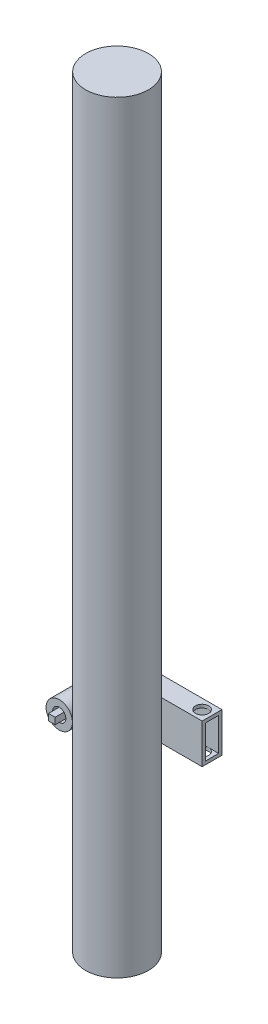
SolidWorks part; units mm, degrees
ref_plane "Front Plane" through (0, 0, 0) normal (0, 0, 1) x (1, 0, 0)
ref_plane "Top Plane" through (0, 0, 0) normal (0, 1, 0) x (1, 0, 0)
ref_plane "Right Plane" through (0, 0, 0) normal (1, 0, 0) x (0, 0, -1)
sketch "Elevation Bar" plane through (0, 0, 0) normal (0, 1, 0) x (1, 0, 0)
  circle A0 centre (0, 0) radius 30.226
  dimension "D1" = 60.452
extrude "Elevation Bar Part" add sketch "Elevation Bar" along normal blind 734.06
sketch "Pole and Drivetrain Pos" plane through (0, 0, 0) normal (0, 0, 1) x (1, 0, 0)
  line L0 (0, 0) -> (172.1794, 0) construction
  line L1 (-30.226, 0) -> (-30.226, 734.06) construction
  line L2 (-30.226, 734.06) -> (30.226, 734.06) construction
  line L3 (30.226, 734.06) -> (30.226, 0) construction
  line L4 (30.226, 0) -> (30.226, 734.06) construction
  line L5 (636.651, 41.275) -> (27.051, 41.275) construction
  line L6 (636.651, 53.975) -> (27.051, 53.975)
  line L7 (636.651, 53.975) -> (636.651, 28.575)
  line L8 (636.651, 28.575) -> (27.051, 28.575)
  line L9 (27.051, 53.975) -> (27.051, 28.575)
  line L10 (-30.226, 93.98) -> (30.226, 93.98) construction
  line L11 (33.2486, 0) -> (-33.2486, 0) construction
  line L12 (30.226, 185.42) -> (-30.226, 185.42) construction
  line L13 (30.226, 276.86) -> (-30.226, 276.86) construction
  line L14 (30.226, 368.3) -> (-30.226, 368.3) construction
  line L15 (30.226, 459.74) -> (-30.226, 459.74) construction
  line L16 (30.226, 551.18) -> (-30.226, 551.18) construction
  line L17 (30.226, 642.62) -> (-30.226, 642.62) construction
  line L18 (30.226, 73.152) -> (750.8896, 73.152) construction
  circle A0 centre (579.501, 41.275) radius 41.275 construction
  circle A1 centre (84.201, 41.275) radius 41.275 construction
  circle A2 centre (331.851, 41.275) radius 41.275 construction
  circle A3 centre (84.201, 41.275) radius 25.4
  point P24 (331.851, 41.275)
  point P28 (0, 0)
  point P45 (0, 0)
  dimension "D2" = 82.55
  dimension "D5" = 50.8
  dimension "D1" = 609.6
  dimension "D3" = 25.4
  dimension "D6" = 93.98
  dimension "D7" = 185.42
  dimension "D8" = 276.86
  dimension "D9" = 368.3
  dimension "D10" = 459.74
  dimension "D11" = 551.18
  dimension "D12" = 642.62
  dimension "D13" = 73.152
  dimension "D14" = 57.15
  dimension "D4" = 57.15
  dimension "D15" = 6.35
sketch "Driving Wheels Geo" plane through (0, 0, 0) normal (0, 0, 1) x (1, 0, 0)
  line L0 (-30.226, 182.88) -> (-30.226, 101.727) construction
  line L1 (55.626, 101.727) -> (30.226, 101.727) construction
  line L2 (-30.226, 0) -> (-30.226, 734.06) construction
  line L3 (30.226, 734.06) -> (30.226, 0) construction
  line L5 (30.226, 101.727) -> (-30.226, 101.727) construction
  line L6 (-30.226, 182.88) -> (30.226, 101.727) construction
  line L7 (31.8135, 101.727) -> (-30.226, 182.88) construction
  line L8 (30.226, 227.417) -> (203.668, 53.975) construction
  line L9 (-42.926, 195.58) -> (44.8729, 195.58) construction
  line L10 (30.226, 73.152) -> (750.8896, 73.152) construction
  line L11 (636.651, 53.975) -> (27.051, 53.975) construction
  line L14 (-42.926, 170.18) -> (44.8729, 170.18) construction
  line L15 (44.8729, 170.18) -> (44.8729, 195.58) construction
  line L16 (81.026, 28.575) -> (81.026, 257.175) construction
  line L17 (32.1729, 195.58) -> (57.5729, 195.58) construction
  line L18 (32.1729, 195.58) -> (32.1729, 170.18) construction
  line L19 (32.1729, 170.18) -> (57.5729, 170.18) construction
  line L20 (57.5729, 195.58) -> (57.5729, 170.18) construction
  line L21 (32.1729, 195.58) -> (57.5729, 170.18) construction
  line L22 (32.1729, 170.18) -> (57.5729, 195.58) construction
  line L23 (636.651, 28.575) -> (27.051, 28.575) construction
  line L24 (284.226, 257.175) -> (81.026, 257.175) construction
  line L25 (284.226, 257.175) -> (284.226, 53.975) construction
  line L26 (81.026, 257.175) -> (30.226, 257.175) construction
  circle A1 centre (55.626, 101.727) radius 25.4
  circle A3 centre (-42.926, 182.88) radius 12.7
  circle A4 centre (81.026, 104.775) radius 50.8 construction
  circle A5 centre (55.626, 101.727) radius 23.8125 construction
  circle A7 centre (284.226, 257.175) radius 203.2 construction
  point P28 (44.8729, 182.88)
  dimension "D1" = 50.8
  dimension "D2" = 1.5875
  dimension "D3" = 52.603
  dimension "D4" = 3.175
  dimension "D5" = 182.88
  dimension "D8" = 101.6
  dimension "D6" = 25.4
  dimension "D13" = 3.175
  dimension "D14" = 50.8
  dimension "D16" = 406.4
  dimension "D7" = 81.153
  dimension "D9" = 45
  dimension "D10" = 53.317
  dimension "D11" = 25.4
  dimension "D12" = 47.752
ref_plane "Plane1" through (0, 182.88, 0) normal (0, 1, 0) x (1, 0, 0)
sketch "Clamp Geo" plane through (0, 182.88, 0) normal (0, 1, 0) x (1, 0, 0)
  line L0 (-42.926, -19.8438) -> (-42.926, 50.8635) construction
  line L3 (27.051, 228.6) -> (27.051, -228.6) construction
  line L4 (50.0464, 31.8135) -> (-49.276, 31.8135)
  line L5 (50.0464, 31.8135) -> (50.0464, 50.8635)
  line L6 (50.0464, 50.8635) -> (-49.276, 50.8635)
  line L7 (-49.276, 31.8135) -> (-49.276, 50.8635)
  line L10 (-46.101, 50.8635) -> (-39.751, 50.8635)
  line L11 (-46.101, 50.8635) -> (-46.101, -19.8438)
  line L12 (-46.101, -19.8438) -> (-39.751, -19.8438)
  line L13 (-39.751, 50.8635) -> (-39.751, -19.8438)
  line L14 (-55.626, 12.7) -> (-30.226, 12.7) construction
  line L15 (-55.626, 12.7) -> (-55.626, -12.7) construction
  line L16 (-55.626, -12.7) -> (-30.226, -12.7) construction
  line L17 (-30.226, 12.7) -> (-30.226, -12.7) construction
  line L18 (-55.626, 12.7) -> (-30.226, -12.7) construction
  line L19 (-55.626, -12.7) -> (-30.226, 12.7) construction
  line L20 (0, -30.226) -> (0, 30.226) construction
  line L21 (-30.226, 0) -> (30.226, 0) construction
  line L22 (-46.101, 46.101) -> (-42.926, 46.101) construction
  line L23 (-39.751, 41.3385) -> (-46.101, 41.3385)
  line L24 (-46.101, 41.3385) -> (-46.101, 50.8635) construction
  line L25 (-39.751, 31.8135) -> (-39.751, 50.8635) construction
  line L26 (50.0464, 41.3385) -> (40.5214, 41.3385) construction
  circle A0 centre (0, 0) radius 30.226 construction
  circle A3 centre (-42.926, 46.101) radius 1.8288
  circle A5 centre (-42.926, 36.576) radius 1.8288
  circle A6 centre (40.5214, 41.3385) radius 6.35
  circle A7 centre (40.5214, 41.3385) radius 13.4704 construction
  point P14 (-42.926, 0)
  point P32 (-39.751, 41.3385)
  point P34 (-46.101, 41.3385)
  point P36 (-42.926, 41.3385)
  point P42 (50.0464, 41.3385)
  dimension "D1" = 60.452
  dimension "D4" = 1.5875
  dimension "D7" = 3.6576
  dimension "D8" = 3.175
  dimension "D10" = 12.7
  dimension "D11" = 3.175
  dimension "D2" = 457.2
  dimension "D3" = 19.05
  dimension "D5" = 6.35
  dimension "D6" = 25.4
  dimension "D9" = 99.3224
  dimension "D13" = 7.1437
sketch "Locked Setting Geo" plane through (0, 182.88, 0) normal (0, 1, 0) x (1, 0, 0)
  line L0 (30.2525, 144.301) -> (91.1428, 108.3583) construction
  line L1 (27.477, 37.9778) -> (77.9656, 123.5104)
  line L2 (27.477, 37.9778) -> (43.8821, 28.2941)
  line L3 (43.8821, 28.2941) -> (94.3707, 113.8267)
  line L4 (77.9656, 123.5104) -> (94.3707, 113.8267)
  line L5 (92.7568, 111.0925) -> (89.5289, 105.6242)
  line L6 (92.7568, 111.0925) -> (31.8664, 147.0352)
  line L7 (31.8664, 147.0352) -> (28.6385, 141.5668)
  line L8 (89.5289, 105.6242) -> (28.6385, 141.5668)
  line L9 (64.7337, 138.6948) -> (51.8221, 116.8213) construction
  line L10 (64.7337, 138.6948) -> (42.8602, 151.6064) construction
  line L11 (42.8602, 151.6064) -> (29.9486, 129.7329) construction
  line L12 (51.8221, 116.8213) -> (29.9486, 129.7329) construction
  line L13 (64.7337, 138.6948) -> (29.9486, 129.7329) construction
  line L14 (42.8602, 151.6064) -> (51.8221, 116.8213) construction
  line L17 (88.6555, 113.5135) -> (87.0416, 110.7793) construction
  line L18 (81.3263, 110.466) -> (84.5542, 115.9344)
  line L19 (84.5542, 115.9344) -> (92.7568, 111.0925) construction
  line L20 (73.1238, 115.3079) -> (89.5289, 105.6242) construction
  line L21 (35.6795, 33.1359) -> (40.5214, 41.3385) construction
  line L22 (50.0464, 50.8635) -> (-49.276, 50.8635) construction
  line L23 (-46.101, 50.8635) -> (-46.101, -19.8438) construction
  line L24 (27.051, 228.6) -> (27.051, -228.6) construction
  circle A1 centre (87.0416, 110.7793) radius 1.8288
  circle A2 centre (78.839, 115.6211) radius 1.8288
  circle A3 centre (40.5214, 41.3385) radius 6.35
  point P10 (47.3411, 134.2138)
  point P28 (81.3263, 110.466)
  point P30 (84.5542, 115.9344)
  point P32 (82.9403, 113.2002)
  point P36 (35.6795, 33.1359)
  point P40 (40.5214, 41.3385)
  point P44 (-17.1792, 28.8062)
  dimension "D6" = 3.6576
  dimension "D9" = 12.7
  dimension "D2" = 19.05
  dimension "D3" = 1.5875
  dimension "D4" = 6.35
  dimension "D5" = 25.4
  dimension "D7" = 3.175
  dimension "D8" = 99.3224
  dimension "D10" = 3.175
  dimension "D11" = 50.8635
  dimension "D12" = 67.3197
extrude "Boss-Extrude1" add sketch "Clamp Geo" along normal blind 19.05 and the other way blind 19.05 separate body contours L6 L13 L4 L5 A6 | L11 L6 L7 L4 | L13 L23 L11 L4 A5 | L23 L13 L6 L11 A3 region at (2.3187, 182.88, -41.3385) region at (-42.926, 182.88, -31.928) region at (-47.6885, 182.88, -41.3385) region at (-42.926, 182.88, -41.453)
sketch "Sketch2" plane through (-49.276, 0, 0) normal (-1, 0, 0) x (0, 0, 1)
  line L0 (-41.3385, 201.93) -> (-41.3385, 163.83) construction
  line L1 (-31.8135, 201.93) -> (-50.8635, 201.93) construction
  line L2 (-31.8135, 163.83) -> (-50.8635, 163.83) construction
  line L3 (-31.8135, 163.83) -> (-31.8135, 201.93) construction
  line L4 (-47.6885, 167.005) -> (-34.9885, 167.005)
  line L5 (-47.6885, 167.005) -> (-47.6885, 198.755)
  line L6 (-47.6885, 198.755) -> (-34.9885, 198.755)
  line L7 (-34.9885, 167.005) -> (-34.9885, 198.755)
  line L8 (-47.6885, 167.005) -> (-34.9885, 198.755) construction
  line L9 (-47.6885, 198.755) -> (-34.9885, 167.005) construction
  point P6 (-41.3385, 182.88)
  dimension "D1" = 3.175
  dimension "D2" = 3.175
extrude "Cut-Extrude2" cut sketch "Sketch2" against normal up to surface (99.3224 mm away) up to face at (50.0464, 182.88, -41.3385)
sketch "Sketch3" plane through (0, 0, -50.8635) normal (0, 0, -1) x (-1, 0, 0)
  line L2 (39.7129, 179.6669) -> (46.1391, 179.6669)
  line L3 (39.7129, 179.6669) -> (39.7129, 186.0931)
  line L4 (39.7129, 186.0931) -> (46.1391, 186.0931)
  line L5 (46.1391, 179.6669) -> (46.1391, 186.0931)
  line L6 (39.7129, 179.6669) -> (46.1391, 186.0931) construction
  line L7 (39.7129, 186.0931) -> (46.1391, 179.6669) construction
  point P0 (42.926, 182.88)
  point P1 (42.926, 182.88)
  dimension "D1" = 6.4262
extrude "Cut-Extrude3" cut sketch "Sketch3" against normal up to surface (19.05 mm away) up to face at (0.3852, 182.88, -31.8135)
extrude "Boss-Extrude2" add sketch "Clamp Geo<3>" along normal blind 3.175 and the other way blind 3.175 separate body contours L13 L4 L11 L12 | L13 L23 L11 L4 A5 | L23 L13 L6 L11 A3 region at (-42.926, 182.88, -5.9849) region at (-42.926, 182.88, -31.928) region at (-42.926, 182.88, -41.453)
sketch "Clamp Geo<3>" plane through (0, 182.88, 0) normal (0, 1, 0) x (1, 0, 0) same geometry as "Clamp Geo"
sketch "Custom Driven Flywheel" plane through (0, 0, 0) normal (0, 0, 1) x (1, 0, 0)
  circle A0 centre (-42.926, 182.88) radius 12.7 construction
  circle A1 centre (-42.926, 182.88) radius 12.7
  circle A2 centre (-42.926, 182.88) radius 6.35
  dimension "D1" = 12.7
extrude "Boss-Extrude3" add sketch "Custom Driven Flywheel" along normal mid plane 25.4 separate body
sketch "Sketch8" plane through (0, 167.005, 0) normal (0, 1, 0) x (1, 0, 0)
  line L0 (-42.926, 47.6885) -> (-42.926, 34.9885) construction
  line L1 (-49.276, 34.9885) -> (-36.576, 34.9885) construction
  line L2 (-49.276, 34.9885) -> (-49.276, 47.6885)
  line L3 (-49.276, 47.6885) -> (-36.576, 47.6885) construction
  line L4 (-36.576, 34.9885) -> (-36.576, 47.6885)
  line L5 (-36.576, 41.3385) -> (-42.926, 41.3385) construction
  line L6 (-42.926, 41.3385) -> (-49.276, 41.3385) construction
  line L7 (-43.8339, 34.9885) -> (-49.276, 34.9885)
  line L8 (-43.8339, 47.6885) -> (-49.276, 47.6885)
  line L9 (-42.0181, 34.9885) -> (-36.576, 34.9885)
  line L10 (-42.0181, 47.6885) -> (-36.576, 47.6885)
  arc A0 (-43.8339, 47.6885) -> (-42.0181, 47.6885) centre (-42.926, 46.101) ccw construction
  arc A2 (-42.0181, 34.9885) -> (-43.8339, 34.9885) centre (-42.926, 36.576) ccw construction
  arc A3 (-43.8339, 47.6885) -> (-42.0181, 47.6885) centre (-42.926, 46.101) ccw
  arc A4 (-42.0181, 34.9885) -> (-43.8339, 34.9885) centre (-42.926, 36.576) ccw
extrude "Boss-Extrude5" add sketch "Sketch8" along normal up to surface (15.875 mm away) separate body up to plane "Plane1"
sketch "Sketch10" plane through (0, 182.88, 0) normal (0, 1, 0) x (1, 0, 0)
  line L0 (-36.576, 41.3385) -> (-49.276, 41.3385) construction
  line L1 (-36.576, 34.9885) -> (-36.576, 47.6885) construction
  line L2 (-49.276, 47.6885) -> (-49.276, 34.9885) construction
  line L3 (-49.276, 34.9885) -> (-43.8339, 34.9885) construction
  line L4 (-46.1391, 34.9885) -> (-39.7129, 34.9885)
  line L5 (-46.1391, 34.9885) -> (-46.1391, 47.6885)
  line L6 (-46.1391, 47.6885) -> (-39.7129, 47.6885)
  line L7 (-39.7129, 34.9885) -> (-39.7129, 47.6885)
  line L8 (-46.1391, 34.9885) -> (-39.7129, 47.6885) construction
  line L9 (-46.1391, 47.6885) -> (-39.7129, 34.9885) construction
  point P6 (-42.926, 41.3385)
  dimension "D1" = 6.4262
extrude "Cut-Extrude5" cut sketch "Sketch10" against normal blind 6.3881
ref_plane "Plane2" through (0, 0, 210.82) normal (0, 0, 1) x (1, 0, 0)
ref_plane "Plane3" through (0, 0, 166.37) normal (0, 0, 1) x (1, 0, 0)
sketch "Sketch12" plane through (0, 0, 166.37) normal (0, 0, 1) x (1, 0, 0)
  line L0 (636.651, 41.275) -> (27.051, 41.275) construction
  line L1 (636.651, 41.275) -> (27.051, 41.275) construction
  line L2 (84.201, 41.275) -> (96.901, 41.275) construction
  line L3 (109.601, 41.275) -> (109.601, 85.2691) construction
  circle A0 centre (84.201, 41.275) radius 25.4 construction
  circle A1 centre (84.201, 41.275) radius 25.4
  circle A2 centre (55.626, 101.727) radius 21.1667
  circle A4 centre (86.8604, 107.4259) radius 10.5833
  circle A5 centre (128.651, 41.275) radius 19.05
  circle A7 centre (86.8604, 107.4259) radius 21.1667
  circle A8 centre (109.601, 85.2691) radius 10.5833
  circle A9 centre (109.601, 85.2691) radius 25.4
  circle A10 centre (84.201, 41.275) radius 3.175 construction
  circle A11 centre (96.901, 41.275) radius 3.175 construction
  circle A12 centre (109.601, 41.275) radius 3.175 construction
  circle A13 centre (122.301, 41.275) radius 3.175 construction
  circle A14 centre (135.001, 41.275) radius 3.175 construction
  circle A15 centre (147.701, 41.275) radius 3.175 construction
  circle A16 centre (160.401, 41.275) radius 3.175 construction
  circle A17 centre (173.101, 41.275) radius 3.175 construction
  circle A18 centre (185.801, 41.275) radius 3.175 construction
  circle A19 centre (198.501, 41.275) radius 3.175 construction
  point P3 (55.626, 101.727)
  dimension "D1" = 42.3333
  dimension "D2" = 21.1667
  dimension "D3" = 50.8
  dimension "D4" = 38.1
  dimension "D5" = 42.3333
  dimension "D6" = 21.1667
  dimension "D8" = 6.35
  dimension "D10" = 12.7
  dimension "D9" = 10
sketch "Sketch13" plane through (0, 0, 210.82) normal (0, 0, 1) x (1, 0, 0)
  line L0 (109.601, 72.5691) -> (109.601, 97.9691) construction
  line L2 (90.551, 72.5691) -> (90.551, 97.9691)
  line L4 (154.051, 72.5691) -> (154.051, 97.9691)
  line L5 (147.701, 85.2691) -> (147.701, 41.275) construction
  line L6 (109.601, 85.2691) -> (154.051, 85.2691) construction
  line L7 (90.551, 85.2691) -> (109.601, 85.2691) construction
  line L8 (90.551, 97.9691) -> (109.601, 97.9691)
  line L9 (90.551, 72.5691) -> (109.601, 72.5691)
  line L10 (109.601, 97.9691) -> (154.051, 97.9691)
  line L11 (154.051, 72.5691) -> (109.601, 72.5691)
  circle A0 centre (109.601, 85.2691) radius 3.175 construction
  circle A1 centre (96.901, 85.2691) radius 3.175 construction
  circle A2 centre (147.701, 85.2691) radius 3.175 construction
  point P0 (109.601, 85.2691)
  dimension "D2" = 6.35
  dimension "D3" = 6.35
  dimension "D6" = 6.35
  dimension "D1" = 25.4
  dimension "D4" = 12.7
  dimension "D5" = 6.35
ref_plane "Plane5" through (0, 0, 146.177) normal (0, 0, 1) x (1, 0, 0)
sketch "Sketch15" plane through (0, 0, 146.177) normal (0, 0, 1) x (1, 0, 0)
  line L0 (90.551, 72.5691) -> (109.601, 72.5691) construction
  line L1 (154.051, 72.5691) -> (109.601, 72.5691) construction
  line L2 (154.051, 72.5691) -> (154.051, 97.9691) construction
  line L3 (109.601, 97.9691) -> (154.051, 97.9691) construction
  line L4 (90.551, 97.9691) -> (109.601, 97.9691) construction
  line L5 (90.551, 72.5691) -> (90.551, 97.9691) construction
  line L6 (90.551, 72.5691) -> (109.601, 72.5691)
  line L7 (154.051, 72.5691) -> (109.601, 72.5691)
  line L8 (154.051, 72.5691) -> (154.051, 97.9691)
  line L9 (109.601, 97.9691) -> (154.051, 97.9691)
  line L10 (90.551, 97.9691) -> (109.601, 97.9691)
  line L11 (90.551, 72.5691) -> (90.551, 97.9691)
  line L12 (90.551, 28.575) -> (109.601, 28.575)
  line L13 (154.051, 28.575) -> (109.601, 28.575)
  line L14 (154.051, 28.575) -> (154.051, 53.975)
  line L15 (109.601, 53.975) -> (154.051, 53.975)
  line L16 (90.551, 53.975) -> (109.601, 53.975)
  line L17 (90.551, 28.575) -> (90.551, 53.975)
  line L18 (154.051, 28.575) -> (90.551, 53.975) construction
  line L19 (109.601, 53.975) -> (109.601, 28.575) construction
  line L20 (154.051, 41.275) -> (90.551, 41.275) construction
  circle A0 centre (109.601, 85.2691) radius 3.175 construction
  circle A1 centre (109.601, 85.2691) radius 3.175
  circle A2 centre (109.601, 41.275) radius 3.175 construction
  point P19 (0, 0)
  point P20 (0, 0)
  point P21 (105.5783, 29.1431)
  point P23 (0, 0)
  dimension "D5" = 6.35
  dimension "D1" = 68.3916
  dimension "D2" = 68.3916
  dimension "D3" = 19.05
  dimension "D4" = 25.4
ref_plane "Plane6" through (0, 53.975, 0) normal (0, 1, 0) x (1, 0, 0)
sketch "Sketch16" plane through (0, 53.975, 0) normal (0, 1, 0) x (1, 0, 0)
  line L0 (27.051, -127) -> (27.051, 127)
  line L1 (33.401, 120.65) -> (33.401, 107.95) construction
  line L2 (27.051, 127) -> (39.751, 127)
  line L3 (27.051, 127) -> (27.051, -127)
  line L4 (27.051, -127) -> (39.751, -127)
  line L5 (39.751, 127) -> (39.751, -127)
  line L6 (33.401, 120.65) -> (33.401, 127) construction
  line L7 (135.001, -166.37) -> (135.001, -127) construction
  line L8 (636.651, 0) -> (27.051, 0) construction
  line L9 (128.651, 127) -> (141.351, 127)
  line L14 (128.651, 127) -> (128.651, -127)
  line L15 (128.651, -127) -> (141.351, -127)
  line L16 (141.351, 127) -> (141.351, -127)
  line L17 (128.651, 127) -> (141.351, -127) construction
  line L18 (128.651, -127) -> (141.351, 127) construction
  line L19 (135.001, -120.65) -> (135.001, -107.95) construction
  line L20 (135.001, -127) -> (135.001, -120.65) construction
  circle A0 centre (33.401, 120.65) radius 3.175
  circle A1 centre (33.401, 107.95) radius 3.175
  circle A2 centre (33.401, 95.25) radius 3.175
  circle A3 centre (33.401, 82.55) radius 3.175
  circle A4 centre (33.401, 69.85) radius 3.175
  circle A5 centre (33.401, 57.15) radius 3.175
  circle A6 centre (33.401, 44.45) radius 3.175
  circle A7 centre (33.401, 31.75) radius 3.175
  circle A8 centre (33.401, 19.05) radius 3.175
  circle A9 centre (33.401, 6.35) radius 3.175
  circle A10 centre (33.401, -6.35) radius 3.175
  circle A11 centre (33.401, -19.05) radius 3.175
  circle A12 centre (33.401, -31.75) radius 3.175
  circle A13 centre (33.401, -44.45) radius 3.175
  circle A14 centre (33.401, -57.15) radius 3.175
  circle A15 centre (33.401, -69.85) radius 3.175
  circle A16 centre (33.401, -82.55) radius 3.175
  circle A17 centre (33.401, -95.25) radius 3.175
  circle A18 centre (33.401, -107.95) radius 3.175
  circle A19 centre (33.401, -120.65) radius 3.175
  circle A40 centre (135.001, -120.65) radius 3.175
  circle A41 centre (135.001, -107.95) radius 3.175
  circle A42 centre (135.001, -95.25) radius 3.175
  circle A43 centre (135.001, -82.55) radius 3.175
  circle A44 centre (135.001, -69.85) radius 3.175
  circle A45 centre (135.001, -57.15) radius 3.175
  circle A46 centre (135.001, -44.45) radius 3.175
  circle A47 centre (135.001, -31.75) radius 3.175
  circle A48 centre (135.001, -19.05) radius 3.175
  circle A49 centre (135.001, -6.35) radius 3.175
  circle A50 centre (135.001, 6.35) radius 3.175
  circle A51 centre (135.001, 19.05) radius 3.175
  circle A52 centre (135.001, 31.75) radius 3.175
  circle A53 centre (135.001, 44.45) radius 3.175
  circle A54 centre (135.001, 57.15) radius 3.175
  circle A55 centre (135.001, 69.85) radius 3.175
  circle A56 centre (135.001, 82.55) radius 3.175
  circle A57 centre (135.001, 95.25) radius 3.175
  circle A58 centre (135.001, 107.95) radius 3.175
  circle A59 centre (135.001, 120.65) radius 3.175
  point P3 (27.051, 0)
  point P9 (135.001, -166.37)
  point P51 (135.001, 0)
  point P62 (133.1951, -120.65)
  dimension "D3" = 6.35
  dimension "D1" = 254
  dimension "D2" = 12.7
  dimension "D4" = 6.35
  dimension "D6" = 12.7
  dimension "D10" = 6.35
  dimension "D12" = 12.7
  dimension "D5" = 20
  dimension "D11" = 20
sketch "Sketch17" plane through (0, 0, 0) normal (0, 0, 1) x (1, 0, 0)
  line L1 (27.051, 53.975) -> (38.5846, 105.5388)
  line L3 (52.4916, 118.9059) -> (83.7259, 124.6048)
  line L4 (99.0466, 119.9333) -> (121.7873, 97.7764)
  line L5 (125.7513, 91.9104) -> (141.351, 53.975)
  line L6 (128.651, 53.975) -> (141.351, 53.975) construction
  line L7 (128.651, 53.975) -> (141.351, 53.975)
  line L8 (27.051, 53.975) -> (41.021, 53.975)
  line L9 (636.651, 53.975) -> (27.051, 53.975) construction
  line L10 (41.021, 53.975) -> (41.021, 41.275)
  line L11 (41.021, 41.275) -> (127.381, 41.275)
  line L12 (128.651, 53.975) -> (127.381, 53.975)
  line L13 (127.381, 53.975) -> (127.381, 41.275)
  line L14 (55.626, 101.727) -> (55.626, 41.275)
  line L15 (55.626, 101.727) -> (33.592, 57.15)
  line L16 (33.592, 57.15) -> (55.626, 57.15)
  circle A0 centre (55.626, 101.727) radius 11.1125
  circle A1 centre (86.8604, 107.4259) radius 11.1125
  circle A2 centre (109.601, 85.2691) radius 11.1125
  arc A3 (52.4916, 118.9059) -> (38.5846, 105.5388) centre (55.626, 101.727) ccw
  arc A4 (99.0466, 119.9333) -> (83.7259, 124.6048) centre (86.8604, 107.4259) ccw
  arc A5 (125.7513, 91.9104) -> (121.7873, 97.7764) centre (109.601, 85.2691) ccw
  circle A7 centre (33.592, 57.15) radius 2.4144
  dimension "D1" = 22.225
  dimension "D2" = 6.35
  dimension "D3" = 13.97
  dimension "D4" = 12.7
  dimension "D5" = 13.97
  dimension "D6" = 3.175
equation "\"D4@Pole and Drivetrain Pos\"=\"D14@Pole and Drivetrain Pos\""
equation "\"D5@Sketch17\"=\"D3@Sketch17\""
